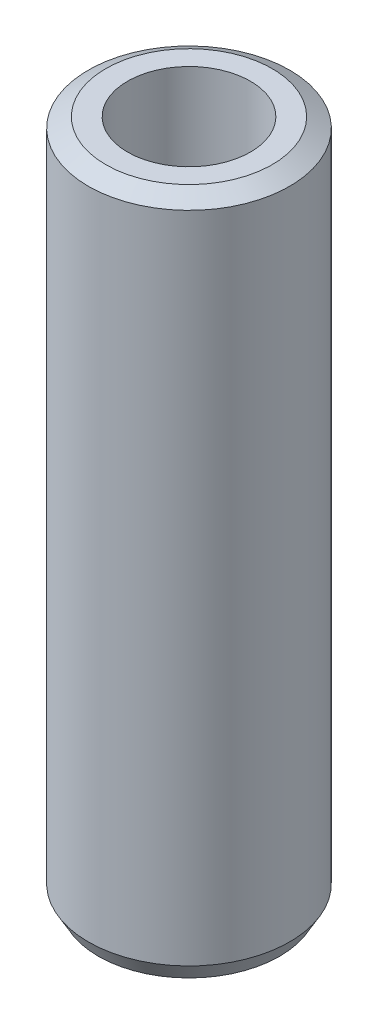
SolidWorks part; units mm, degrees
ref_plane "Front Plane" through (0, 0, 0) normal (0, 0, 1) x (1, 0, 0)
ref_plane "Top Plane" through (0, 0, 0) normal (0, 1, 0) x (1, 0, 0)
ref_plane "Right Plane" through (0, 0, 0) normal (1, 0, 0) x (0, 0, -1)
sketch "Sketch1" plane through (0, 0, 0) normal (0, 1, 0) x (1, 0, 0)
  circle A0 centre (0, 0) radius 27.5
  dimension "SHAFT_OD" = 55
extrude "Boss-Extrude1" add sketch "Sketch1" along normal blind 186.2529
sketch "Sketch2" plane through (0, 0, 0) normal (0, 1, 0) x (1, 0, 0)
  circle A0 centre (0, 0) radius 16.7847
  dimension "BORE_D" = 33.5694
extrude "Cut-Extrude1" cut sketch "Sketch2" along normal through all
chamfer "Chamfer1" distance 2.7277 angle 60.219 2 edges at (0, 186.2529, 27.5) (0, 0, 27.5) first distance on face at (0, 186.2529, 27.5) first distance on face at (0, 0, 16.7847)
